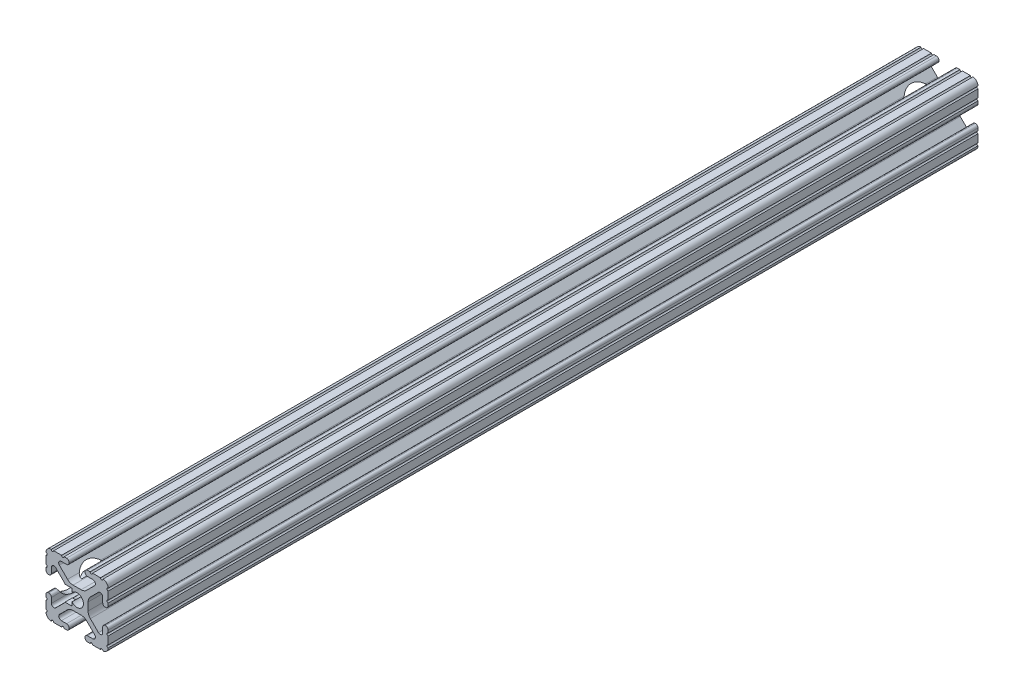
SolidWorks part; units mm, degrees
ref_plane "Front Plane" through (0, 0, 0) normal (0, 0, 1) x (1, 0, 0)
ref_plane "Top Plane" through (0, 0, 0) normal (0, 1, 0) x (1, 0, 0)
ref_plane "Right Plane" through (0, 0, 0) normal (1, 0, 0) x (0, 0, -1)
sketch "Sketch1" plane through (0, 0, 0) normal (0, 0, 1) x (1, 0, 0)
  line L88 (-7.1797, -8.6452) -> (-3.9523, -5.4237)
  line L89 (-1.7093, -4.4958) -> (1.7093, -4.4958)
  line L90 (3.9523, -5.4237) -> (7.1797, -8.6452)
  line L91 (6.4164, -10.4902) -> (4.2875, -10.4902)
  line L92 (3.2385, -11.5392) -> (3.2385, -11.651)
  line L93 (4.2875, -12.7) -> (5.3171, -12.7)
  line L94 (6.3331, -12.7) -> (9.5504, -12.7)
  line L95 (12.7, -9.5504) -> (12.7, -6.3331)
  line L96 (12.7, -5.3171) -> (12.7, -4.2875)
  line L97 (11.651, -3.2385) -> (11.5392, -3.2385)
  line L98 (10.4902, -4.2875) -> (10.4902, -6.4021)
  line L99 (8.7371, -7.1294) -> (5.441, -3.8408)
  line L100 (4.5085, -1.5932) -> (4.5085, 1.5932)
  line L101 (5.441, 3.8408) -> (8.7371, 7.1294)
  line L102 (10.4902, 6.4021) -> (10.4902, 4.2875)
  line L103 (11.5392, 3.2385) -> (11.651, 3.2385)
  line L104 (12.7, 4.2875) -> (12.7, 5.3171)
  line L105 (12.7, 6.3331) -> (12.7, 9.5504)
  line L106 (9.5504, 12.7) -> (6.3331, 12.7)
  line L107 (5.3171, 12.7) -> (4.2875, 12.7)
  line L108 (3.2385, 11.651) -> (3.2385, 11.5392)
  line L109 (4.2875, 10.4902) -> (6.4768, 10.4902)
  line L110 (7.207, 8.7244) -> (3.8983, 5.4232)
  line L111 (1.6558, 4.4958) -> (-1.6558, 4.4958)
  line L112 (-3.8983, 5.4232) -> (-7.207, 8.7244)
  line L113 (-6.4768, 10.4902) -> (-4.2875, 10.4902)
  line L114 (-3.2385, 11.5392) -> (-3.2385, 11.651)
  line L115 (-4.2875, 12.7) -> (-5.3171, 12.7)
  line L116 (-6.3331, 12.7) -> (-9.5504, 12.7)
  line L117 (-12.7, 9.5504) -> (-12.7, 6.3331)
  line L118 (-12.7, 5.3171) -> (-12.7, 4.2875)
  line L119 (-11.651, 3.2385) -> (-11.5392, 3.2385)
  line L120 (-10.4902, 4.2875) -> (-10.4902, 6.4021)
  line L121 (-8.7371, 7.1294) -> (-5.441, 3.8408)
  line L122 (-4.5085, 1.5932) -> (-4.5085, -1.5932)
  line L123 (-5.441, -3.8408) -> (-8.7371, -7.1294)
  line L124 (-10.4902, -6.4021) -> (-10.4902, -4.2875)
  line L125 (-11.5392, -3.2385) -> (-11.651, -3.2385)
  line L126 (-12.7, -4.2875) -> (-12.7, -5.3171)
  line L127 (-12.7, -6.3331) -> (-12.7, -9.5504)
  line L128 (-9.5504, -12.7) -> (-6.3331, -12.7)
  line L129 (-5.3171, -12.7) -> (-4.2875, -12.7)
  line L130 (-3.2385, -11.651) -> (-3.2385, -11.5392)
  line L131 (-4.2875, -10.4902) -> (-6.4164, -10.4902)
  circle A1 centre (0, 0) radius 2.6035
  arc A104 (-7.1797, -8.6452) -> (-6.4164, -10.4902) centre (-6.4164, -9.4098) ccw
  arc A105 (-1.7093, -4.4958) -> (-3.9523, -5.4237) centre (-1.7093, -7.6708) ccw
  arc A106 (3.9523, -5.4237) -> (1.7093, -4.4958) centre (1.7093, -7.6708) ccw
  arc A107 (6.4164, -10.4902) -> (7.1797, -8.6452) centre (6.4164, -9.4098) ccw
  arc A108 (4.2875, -10.4902) -> (3.2385, -11.5392) centre (4.2875, -11.5392) ccw
  arc A109 (3.2385, -11.651) -> (4.2875, -12.7) centre (4.2875, -11.651) ccw
  arc A110 (6.3331, -12.7) -> (5.3171, -12.7) centre (5.8251, -12.7) ccw
  arc A111 (10.5664, -12.6998) -> (9.5504, -12.7) centre (10.0584, -12.7) ccw
  arc A112 (10.5664, -12.6998) -> (12.6998, -10.5664) centre (10.5918, -10.5918) ccw
  arc A113 (12.7, -9.5504) -> (12.6998, -10.5664) centre (12.7, -10.0584) ccw
  arc A114 (12.7, -5.3171) -> (12.7, -6.3331) centre (12.7, -5.8251) ccw
  arc A115 (12.7, -4.2875) -> (11.651, -3.2385) centre (11.651, -4.2875) ccw
  arc A116 (11.5392, -3.2385) -> (10.4902, -4.2875) centre (11.5392, -4.2875) ccw
  arc A117 (8.7371, -7.1294) -> (10.4902, -6.4021) centre (9.4628, -6.4021) ccw
  arc A118 (4.5085, -1.5932) -> (5.441, -3.8408) centre (7.6835, -1.5932) ccw
  arc A119 (5.441, 3.8408) -> (4.5085, 1.5932) centre (7.6835, 1.5932) ccw
  arc A120 (10.4902, 6.4021) -> (8.7371, 7.1294) centre (9.4628, 6.4021) ccw
  arc A121 (10.4902, 4.2875) -> (11.5392, 3.2385) centre (11.5392, 4.2875) ccw
  arc A122 (11.651, 3.2385) -> (12.7, 4.2875) centre (11.651, 4.2875) ccw
  arc A123 (12.7, 6.3331) -> (12.7, 5.3171) centre (12.7, 5.8251) ccw
  arc A124 (12.6998, 10.5664) -> (12.7, 9.5504) centre (12.7, 10.0584) ccw
  arc A125 (12.6998, 10.5664) -> (10.5664, 12.6998) centre (10.5918, 10.5918) ccw
  arc A126 (9.5504, 12.7) -> (10.5664, 12.6998) centre (10.0584, 12.7) ccw
  arc A127 (5.3171, 12.7) -> (6.3331, 12.7) centre (5.8251, 12.7) ccw
  arc A128 (4.2875, 12.7) -> (3.2385, 11.651) centre (4.2875, 11.651) ccw
  arc A129 (3.2385, 11.5392) -> (4.2875, 10.4902) centre (4.2875, 11.5392) ccw
  arc A130 (7.207, 8.7244) -> (6.4768, 10.4902) centre (6.4768, 9.4563) ccw
  arc A131 (1.6558, 4.4958) -> (3.8983, 5.4232) centre (1.6558, 7.6708) ccw
  arc A132 (-3.8983, 5.4232) -> (-1.6558, 4.4958) centre (-1.6558, 7.6708) ccw
  arc A133 (-6.4768, 10.4902) -> (-7.207, 8.7244) centre (-6.4768, 9.4563) ccw
  arc A134 (-4.2875, 10.4902) -> (-3.2385, 11.5392) centre (-4.2875, 11.5392) ccw
  arc A135 (-3.2385, 11.651) -> (-4.2875, 12.7) centre (-4.2875, 11.651) ccw
  arc A136 (-6.3331, 12.7) -> (-5.3171, 12.7) centre (-5.8251, 12.7) ccw
  arc A137 (-10.5664, 12.6998) -> (-9.5504, 12.7) centre (-10.0584, 12.7) ccw
  arc A138 (-10.5664, 12.6998) -> (-12.6998, 10.5664) centre (-10.5918, 10.5918) ccw
  arc A139 (-12.7, 9.5504) -> (-12.6998, 10.5664) centre (-12.7, 10.0584) ccw
  arc A140 (-12.7, 5.3171) -> (-12.7, 6.3331) centre (-12.7, 5.8251) ccw
  arc A141 (-12.7, 4.2875) -> (-11.651, 3.2385) centre (-11.651, 4.2875) ccw
  arc A142 (-11.5392, 3.2385) -> (-10.4902, 4.2875) centre (-11.5392, 4.2875) ccw
  arc A143 (-8.7371, 7.1294) -> (-10.4902, 6.4021) centre (-9.4628, 6.4021) ccw
  arc A144 (-4.5085, 1.5932) -> (-5.441, 3.8408) centre (-7.6835, 1.5932) ccw
  arc A145 (-5.441, -3.8408) -> (-4.5085, -1.5932) centre (-7.6835, -1.5932) ccw
  arc A146 (-10.4902, -6.4021) -> (-8.7371, -7.1294) centre (-9.4628, -6.4021) ccw
  arc A147 (-10.4902, -4.2875) -> (-11.5392, -3.2385) centre (-11.5392, -4.2875) ccw
  arc A148 (-11.651, -3.2385) -> (-12.7, -4.2875) centre (-11.651, -4.2875) ccw
  arc A149 (-12.7, -6.3331) -> (-12.7, -5.3171) centre (-12.7, -5.8251) ccw
  arc A150 (-12.6998, -10.5664) -> (-12.7, -9.5504) centre (-12.7, -10.0584) ccw
  arc A151 (-12.6998, -10.5664) -> (-10.5664, -12.6998) centre (-10.5918, -10.5918) ccw
  arc A152 (-9.5504, -12.7) -> (-10.5664, -12.6998) centre (-10.0584, -12.7) ccw
  arc A153 (-5.3171, -12.7) -> (-6.3331, -12.7) centre (-5.8251, -12.7) ccw
  arc A154 (-4.2875, -12.7) -> (-3.2385, -11.651) centre (-4.2875, -11.651) ccw
  arc A155 (-3.2385, -11.5392) -> (-4.2875, -10.4902) centre (-4.2875, -11.5392) ccw
extrude "Boss-Extrude1" add sketch "Sketch1" along normal mid plane 355.6
ref_plane "Plane1" through (0, 0, 0) normal (0, 1, 0) x (1, 0, 0)
ref_plane "Plane2" through (0, 0, 0) normal (-1, 0, 0) x (0, 0, 1)
sketch "Sketch2" plane through (-12.7, 0, 0) normal (-1, 0, 0) x (0, 0, 1)
  line L0 (177.8, -6.3331) -> (177.8, -9.5504) construction
  line L1 (177.8, -6.3331) -> (177.8, -9.5504) construction
  line L2 (177.8, 12.7) -> (-177.8, 12.7) construction
  line L3 (177.8, -12.7) -> (-177.8, -12.7) construction
  line L4 (177.8, 12.7) -> (-177.8, 12.7) construction
  line L5 (177.8, -12.7) -> (-177.8, -12.7) construction
  line L6 (137.5638, -12.7) -> (137.5638, 12.7) construction
  line L7 (226.3476, 0) -> (105.4883, 0) construction
  line L9 (177.8, 3.175) -> (168.5925, 3.175)
  line L10 (177.8, 3.175) -> (177.8, -3.175)
  line L11 (177.8, -3.175) -> (168.5925, -3.175)
  line L12 (168.5925, 3.175) -> (168.5925, -3.175)
  line L13 (177.8, 3.175) -> (168.5925, -3.175) construction
  line L14 (177.8, -3.175) -> (168.5925, 3.175) construction
  circle A0 centre (168.5925, 0) radius 6.985
  point P11 (173.1962, 0)
  point P18 (167.6652, 0)
  line M10 (177.8, -6.3331) -> (-177.8, -6.3331)
  dimension "D1" = 13.97
  dimension "D2" = 6.35
  dimension "D3" = 9.2075
extrude "Cut-Extrude1" cut sketch "Sketch2" against normal blind 10.668 contours L11 A0 L9 L12 | A0 L11 L10 L9 | A0 L11 L12 L9 M10 | A0 M10 region at (-12.7, 0, 176.5542) region at (-12.7, 0, 171.9645) region at (-12.7, 0.158, 167.2559) region at (-12.7, -6.5949, 168.5925)
mirror "Mirror1" about plane through (0, 0, 0) normal (0, 0, 1) of "Cut-Extrude1"
